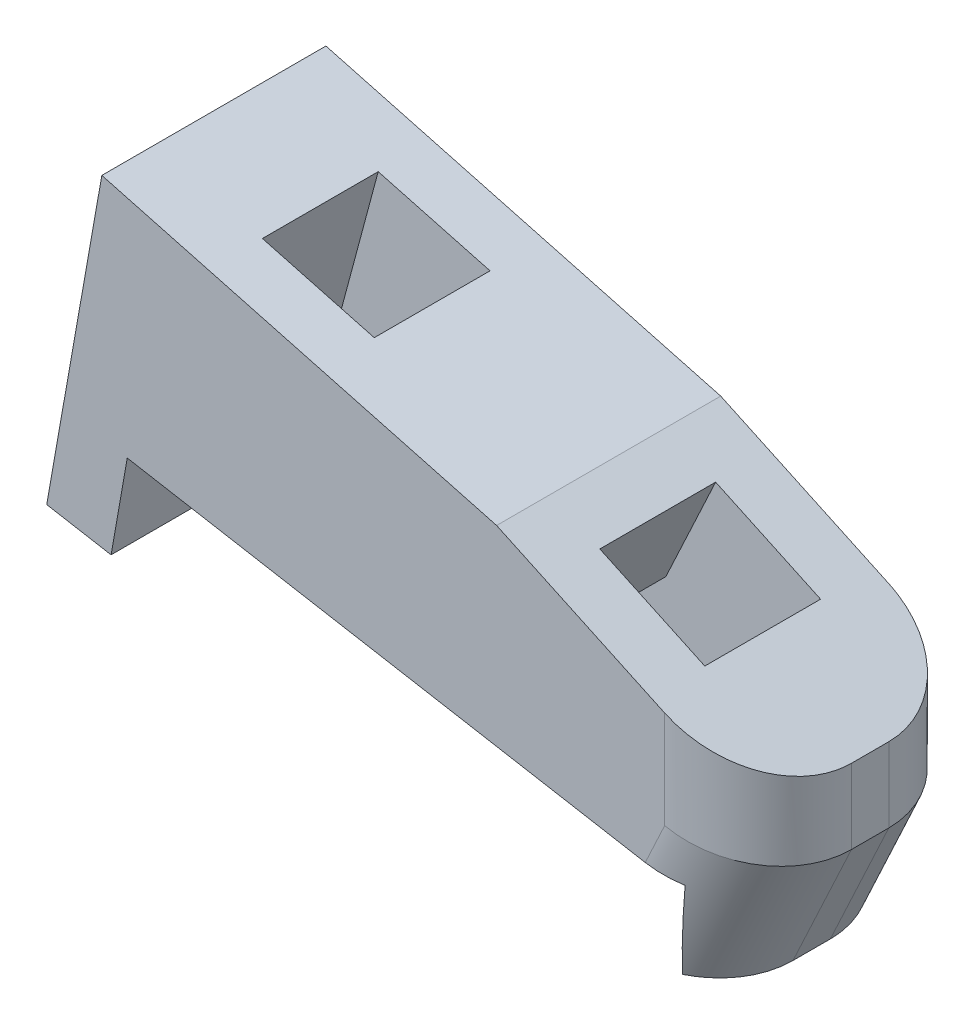
SolidWorks part; units mm, degrees
ref_plane "Front Plane" through (0, 0, 0) normal (0, 0, 1) x (1, 0, 0)
ref_plane "Top Plane" through (0, 0, 0) normal (0, 1, 0) x (1, 0, 0)
ref_plane "Right Plane" through (0, 0, 0) normal (1, 0, 0) x (0, 0, -1)
sketch "Sketch1" plane through (0, 0, 0) normal (0, 0, 1) x (1, 0, 0)
  line L0 (5.9016, 38.1744) -> (2.9496, 21.4327)
  line L1 (2.9496, 21.4327) -> (6.3964, 20.8249)
  line L2 (6.3964, 20.8249) -> (7.2647, 25.749)
  line L3 (7.2647, 25.749) -> (36.8089, 20.5395)
  line L4 (36.8089, 20.5395) -> (35.9407, 15.6155)
  line L5 (35.9407, 15.6155) -> (37.9103, 15.2682)
  line L6 (37.9103, 15.2682) -> (41.0409, 21.9818)
  line L7 (41.0409, 21.9818) -> (41.0409, 25.9818)
  line L8 (41.0409, 25.9818) -> (27.0409, 32.5102)
  line L9 (27.0409, 32.5102) -> (5.9016, 38.1744)
  dimension "D1" = 17
  dimension "D2" = 3.5
  dimension "D3" = 5
  dimension "D4" = 30
  dimension "D5" = 5
  dimension "D6" = 15
  dimension "D7" = 155
  dimension "D8" = 170
  dimension "D9" = 14
  dimension "D10" = 4
  dimension "D11" = 2
extrude "Boss-Extrude1" add sketch "Sketch1" along normal blind 6 and the other way blind 6 contours L8 L9 L0 L1 L2 L3 L4 L5 L6 L7
sketch "Sketch2" plane through (4.6224, 26.2149, 0) normal (-0.1736, -0.9848, 0) x (0.9848, -0.1736, 0)
  line L0 (2.683, -6) -> (2.683, 6) construction
  line L1 (5.083, 3.1) -> (11.283, 3.1)
  line L2 (5.083, 3.1) -> (5.083, -3.1)
  line L3 (5.083, -3.1) -> (11.283, -3.1)
  line L4 (11.283, 3.1) -> (11.283, -3.1)
  line L5 (5.083, 3.1) -> (11.283, -3.1) construction
  line L6 (5.083, -3.1) -> (11.283, 3.1) construction
  line L7 (20.083, 3.1) -> (26.283, 3.1)
  line L8 (20.083, 3.1) -> (20.083, -3.1)
  line L9 (20.083, -3.1) -> (26.283, -3.1)
  line L10 (26.283, 3.1) -> (26.283, -3.1)
  line L11 (20.083, 3.1) -> (26.283, -3.1) construction
  line L12 (20.083, -3.1) -> (26.283, 3.1) construction
  line L13 (8.183, 0) -> (23.183, 0) construction
  line L14 (8.183, 0) -> (2.683, 0) construction
  point P0 (8.183, 0)
  point P5 (23.183, 0)
  dimension "D1" = 6.2
  dimension "D2" = 6.2
  dimension "D3" = 6.2
  dimension "D4" = 6.2
  dimension "D5" = 15
  dimension "D6" = 5.5
extrude "Cut-Extrude1" cut sketch "Sketch2" against normal blind 3.25
sketch "Sketch3" plane through (9.9389, 37.0926, 0) normal (0.2588, 0.9659, 0) x (0.9659, -0.2588, 0)
  line L0 (4.8203, 0) -> (-4.1797, 0) construction
  line L1 (1.7203, 3.1) -> (7.9203, 3.1)
  line L2 (1.7203, 3.1) -> (1.7203, -3.1)
  line L3 (1.7203, -3.1) -> (7.9203, -3.1)
  line L4 (7.9203, 3.1) -> (7.9203, -3.1)
  line L5 (1.7203, 3.1) -> (7.9203, -3.1) construction
  line L6 (1.7203, -3.1) -> (7.9203, 3.1) construction
  line L7 (-4.1797, 6) -> (-4.1797, -6) construction
  point P0 (4.8203, 0)
  dimension "D1" = 6.2
  dimension "D2" = 6.2
  dimension "D3" = 9
extrude "Cut-Extrude2" cut sketch "Sketch3" against normal blind 3.25
sketch "Sketch4" plane through (17.2818, 37.0609, 0) normal (0.4226, 0.9063, 0) x (0.9063, -0.4226, 0)
  line L0 (16.768, 0) -> (10.768, 0) construction
  line L1 (13.668, 3.1) -> (19.868, 3.1)
  line L2 (13.668, 3.1) -> (13.668, -3.1)
  line L3 (13.668, -3.1) -> (19.868, -3.1)
  line L4 (19.868, 3.1) -> (19.868, -3.1)
  line L5 (13.668, 3.1) -> (19.868, -3.1) construction
  line L6 (13.668, -3.1) -> (19.868, 3.1) construction
  line L7 (10.768, 6) -> (10.768, -6) construction
  point P0 (16.768, 0)
  dimension "D1" = 6
  dimension "D2" = 6.2
  dimension "D3" = 6.2
extrude "Cut-Extrude3" cut sketch "Sketch4" against normal blind 3.25
fillet "Fillet1" radius 5 4 edges at (39.4756, 18.625, -6) (41.0409, 23.9818, -6) (39.4756, 18.625, 6) (41.0409, 23.9818, 6)
sketch "Sketch5" plane through (9.0978, 33.9534, 0) normal (0.2588, 0.9659, 0) x (0.9659, -0.2588, 0)
  line L1 (1.7203, 3.1) -> (7.9203, 3.1)
  line L2 (1.7203, 3.1) -> (1.7203, -3.1)
  line L3 (1.7203, -3.1) -> (7.9203, -3.1)
  line L4 (7.9203, 3.1) -> (7.9203, -3.1)
extrude "Cut-Extrude4" cut sketch "Sketch5" against normal through all
sketch "Sketch6" plane through (15.9083, 34.1154, 0) normal (0.4226, 0.9063, 0) x (0.9063, -0.4226, 0)
  line L1 (13.668, 3.1) -> (19.868, 3.1)
  line L2 (13.668, 3.1) -> (13.668, -3.1)
  line L3 (13.668, -3.1) -> (19.868, -3.1)
  line L4 (19.868, 3.1) -> (19.868, -3.1)
extrude "Cut-Extrude5" cut sketch "Sketch6" against normal through all
